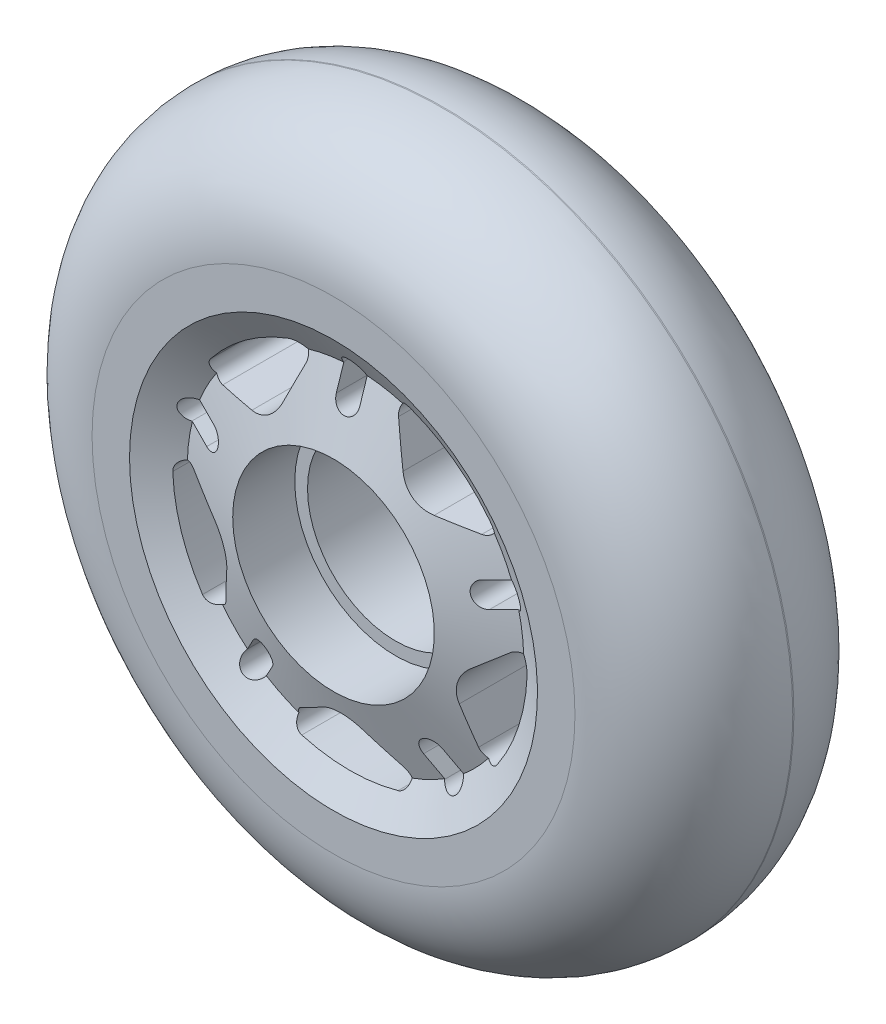
SolidWorks part; units mm, degrees
ref_plane "Front Plane" through (0, 0, 0) normal (0, 0, 1) x (1, 0, 0)
ref_plane "Top Plane" through (0, 0, 0) normal (0, 1, 0) x (1, 0, 0)
ref_plane "Right Plane" through (0, 0, 0) normal (1, 0, 0) x (0, 0, -1)
sketch "Sketch1" plane through (0, 0, 0) normal (0, 0, 1) x (1, 0, 0)
  circle A0 centre (0, 0) radius 37.9997
  dimension "D1" = 75.9993
extrude "Boss-Extrude1" add sketch "Sketch1" along normal mid plane 23.749
fillet "Fillet11" radius 11.811 2 edges at (37.9997, 0, -11.8745) (37.9997, 0, 11.8745)
sketch "Sketch5" plane through (0, 0, -11.8745) normal (0, 0, -1) x (-1, 0, 0)
  circle A0 centre (0, 0) radius 10.9347
  dimension "D1" = 21.8694
extrude "Cut-Extrude1" cut sketch "Sketch5" against normal blind 6.731
sketch "Sketch7" plane through (0, 0, -5.1435) normal (0, 0, -1) x (-1, 0, 0)
  circle A0 centre (0, 0) radius 9.5504
  dimension "D1" = 19.1008
extrude "Cut-Extrude3" cut sketch "Sketch7" against normal through all
mirror "Mirror1" about plane through (0, 0, 0) normal (0, 0, 1) of "Cut-Extrude1"
sketch "Sketch9" plane through (0, 0, 0) normal (1, 0, 0) x (0, 0, -1)
  line L0 (-11.8745, 26.1887) -> (-11.8745, -26.1887) construction
  line L1 (-11.8745, 22.1247) -> (-11.8745, 10.9347)
  line L2 (-11.8745, 26.1887) -> (-11.8745, 22.1247) construction
  line L3 (-11.8745, 22.1247) -> (-11.8745, 18.2385) construction
  line L4 (-11.8745, 10.9347) -> (-11.8745, -10.9347) construction
  line L5 (-11.8745, 18.2385) -> (-9.4869, 18.2385) construction
  line L6 (-11.8745, 22.1247) -> (-9.4869, 18.2385)
  line L7 (-9.4869, 18.2385) -> (-11.8745, 10.9347)
  line L8 (0, 0) -> (-23.0327, 0) construction
  line L9 (-11.8745, 10.9347) -> (-11.8745, -10.9347) construction
  dimension "D1" = 2.3876
  dimension "D2" = 3.8862
  dimension "D3" = 4.064
revolve "Cut-Revolve1" cut sketch "Sketch9" angle 360 about L8
sketch "Sketch10" plane through (0, 0, 11.8745) normal (0, 0, 1) x (1, 0, 0)
  line L0 (0, -12.573) -> (-7.7089, -17.6162)
  line L1 (0, -12.573) -> (7.7089, -17.6162)
  line L2 (0, 0) -> (0, 7.3344) construction
  arc A0 (-7.7089, -17.6162) -> (7.7089, -17.6162) centre (0, 0) ccw
  circle A1 centre (0, 0) radius 37.9997 construction
  circle A2 centre (0, 0) radius 37.9997 construction
  circle A3 centre (0, 0) radius 10.9347 construction
  dimension "D1" = 18.7706
  dimension "D2" = 12.573
  dimension "D3" = 15.4178
extrude "Cut-Extrude4" cut sketch "Sketch10" against normal through all
fillet "Fillet12" radius 3.81 1 edges at (0, -12.573, -0.2678)
fillet "Fillet14" radius 1.27 2 edges at (7.7089, -17.6162, -0.8895) (-7.7089, -17.6162, -0.8895)
sketch "Sketch11" plane through (0, 0, 0) normal (0, 1, 0) x (1, 0, 0)
  line L0 (0, 0) -> (0, -14.7479) construction
pattern_circular "CirPattern1" count 5 over 360 about axis through (0, 0, 11.8745) along (0, 0, 1) of "Cut-Extrude4", "Fillet12", "Fillet14" reverse direction yes
mirror "Mirror3" about plane through (0, 0, 0) normal (0, 0, 1) of "Cut-Revolve1"
sketch "Sketch12" plane through (0, 0, 11.8745) normal (0, 0, 1) x (1, 0, 0)
  line L0 (14.9301, 4.8511) -> (17.3458, 5.636) construction
  line L1 (14.5377, 6.0589) -> (16.9534, 6.8438)
  line L2 (15.3226, 3.6433) -> (17.7383, 4.4282)
  line L3 (0, 0) -> (17.3458, 5.636) construction
  arc A0 (14.5377, 6.0589) -> (15.3226, 3.6433) centre (14.9301, 4.8511) ccw
  arc A1 (17.7383, 4.4282) -> (16.9534, 6.8438) centre (17.3458, 5.636) ccw
  arc A3 (18.2305, 0.5381) -> (15.0651, 10.2803) centre (0, 0) ccw construction
  point P2 (16.138, 5.2435)
  dimension "D1" = 2.54
  dimension "D2" = 2.54
extrude "Cut-Extrude5" cut sketch "Sketch12" against normal through all
pattern_circular "CirPattern2" count 5 over 360 about axis through (0, 0, 11.8745) along (0, 0, 1) of "Cut-Extrude5"
